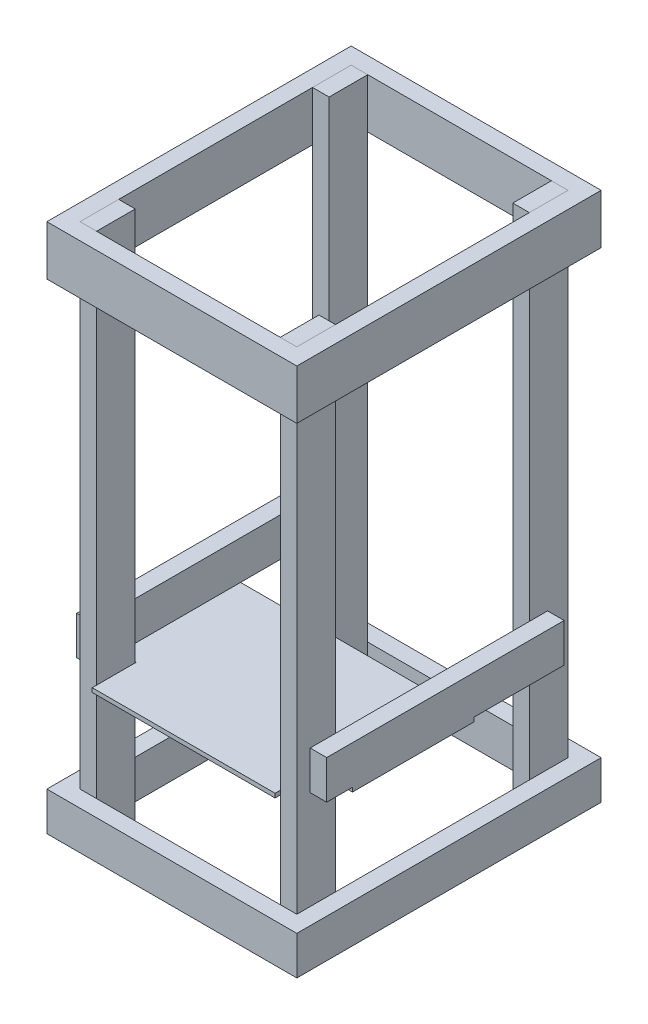
SolidWorks part; units mm, degrees
ref_plane "Front Plane" through (0, 0, 0) normal (0, 0, 1) x (1, 0, 0)
ref_plane "Top Plane" through (0, 0, 0) normal (0, 1, 0) x (1, 0, 0)
ref_plane "Right Plane" through (0, 0, 0) normal (1, 0, 0) x (0, 0, -1)
sketch "Sketch1" plane through (0, 0, 0) normal (0, 1, 0) x (1, 0, 0)
  line L0 (-130.4222, 311.9) -> (-130.4222, 350) construction
  line L1 (-287.5, 350) -> (287.5, 350)
  line L2 (-287.5, 350) -> (-287.5, -350)
  line L3 (-287.5, -350) -> (287.5, -350)
  line L4 (287.5, 350) -> (287.5, -350)
  line L5 (-287.5, 350) -> (287.5, -350) construction
  line L6 (-287.5, -350) -> (287.5, 350) construction
  line L7 (-249.4, 311.9) -> (249.4, 311.9)
  line L8 (-249.4, 311.9) -> (-249.4, -311.9)
  line L9 (-249.4, -311.9) -> (249.4, -311.9)
  line L10 (249.4, 311.9) -> (249.4, -311.9)
  line L11 (-249.4, 311.9) -> (249.4, -311.9) construction
  line L12 (-249.4, -311.9) -> (249.4, 311.9) construction
  line L14 (-249.4, 37.6035) -> (-287.5, 37.6035) construction
  line L16 (-62.8311, -311.9) -> (-62.8311, -350) construction
  line L18 (249.4, -90.9147) -> (287.5, -90.9147) construction
  point P0 (0, 0)
  point P6 (0, 0)
  dimension "D1" = 575
  dimension "D2" = 700
  dimension "D3" = 38.1
extrude "Boss-Extrude1" add sketch "Sketch1" along normal blind 114.3
sketch "Sketch2" plane through (0, 114.3, 0) normal (0, -1, 0) x (1, 0, 0)
  line L1 (-249.4, 311.9) -> (-211.3, 311.9)
  line L2 (-249.4, 311.9) -> (-249.4, 223)
  line L3 (-249.4, 223) -> (-211.3, 223)
  line L4 (-211.3, 311.9) -> (-211.3, 223)
  line L5 (-249.4, -311.9) -> (-211.3, -311.9)
  line L6 (-249.4, -311.9) -> (-249.4, -223)
  line L7 (-249.4, -223) -> (-211.3, -223)
  line L8 (-211.3, -311.9) -> (-211.3, -223)
  line L9 (249.4, 311.9) -> (211.3, 311.9)
  line L10 (249.4, 311.9) -> (249.4, 223)
  line L11 (249.4, 223) -> (211.3, 223)
  line L12 (211.3, 311.9) -> (211.3, 223)
  line L19 (249.4, -311.9) -> (211.3, -311.9)
  line L20 (249.4, -311.9) -> (249.4, -223)
  line L21 (249.4, -223) -> (211.3, -223)
  line L22 (211.3, -311.9) -> (211.3, -223)
  dimension "D1" = 38.1
  dimension "D2" = 88.9
extrude "Boss-Extrude2" add sketch "Sketch2" along normal blind 1219.2 separate body
sketch "Sketch3" plane through (0, -1104.9, 0) normal (0, -1, 0) x (1, 0, 0)
  line L0 (249.4, -311.9) -> (-249.4, -311.9) construction
  line L1 (249.4, 311.9) -> (249.4, -311.9) construction
  line L2 (-249.4, 311.9) -> (249.4, 311.9) construction
  line L3 (-249.4, -311.9) -> (-249.4, 311.9) construction
  line L4 (287.5, -350) -> (287.5, 350)
  line L5 (287.5, 350) -> (-287.5, 350)
  line L6 (-287.5, 350) -> (-287.5, -350)
  line L7 (-287.5, -350) -> (287.5, -350)
  line L8 (287.5, -350) -> (287.5, 350)
  line L9 (287.5, 350) -> (-287.5, 350)
  line L10 (-287.5, 350) -> (-287.5, -350)
  line L11 (-287.5, -350) -> (287.5, -350)
  line L12 (249.4, -311.9) -> (-249.4, -311.9)
  line L13 (249.4, 311.9) -> (249.4, -311.9)
  line L14 (-249.4, 311.9) -> (249.4, 311.9)
  line L15 (-249.4, -311.9) -> (-249.4, 311.9)
  dimension "D1" = 0
extrude "Boss-Extrude3" add sketch "Sketch3" against normal blind 88.9
ref_plane "Plane1" through (0, -788.9875, 0) normal (0, 1, 0) x (1, 0, 0)
sketch "Sketch7" plane through (0, -788.9875, 0) normal (0, 1, 0) x (1, 0, 0)
  line L0 (-249.4, 264.9186) -> (-287.5, 264.9186)
  line L1 (-249.4, 311.9) -> (-249.4, -311.9) construction
  line L2 (-287.5, 350) -> (-287.5, -350) construction
  line L3 (-287.5, 264.9186) -> (-287.5, -281.3159)
  line L4 (-287.5, -281.3159) -> (-249.4, -281.3159)
  line L5 (-249.4, 311.9) -> (-249.4, -311.9) construction
  line L6 (-249.4, -281.3159) -> (-249.4, 264.9186)
  line L7 (249.4, 264.9186) -> (287.5, 264.9186)
  line L8 (249.4, -311.9) -> (249.4, 311.9) construction
  line L9 (287.5, -350) -> (287.5, 350) construction
  line L10 (287.5, 264.9186) -> (287.5, -281.3159)
  line L11 (287.5, -281.3159) -> (249.4, -281.3159)
  line L12 (249.4, -281.3159) -> (249.4, 264.9186)
extrude "Boss-Extrude4" add sketch "Sketch7" along normal blind 88.9
sketch "Sketch8" plane through (0, -788.9875, 0) normal (0, -1, 0) x (1, 0, 0)
  line L1 (287.5, -350) -> (287.5, 350) construction
  line L7 (-287.5, 350) -> (-287.5, -350) construction
  line L8 (-287.5, 222) -> (-287.5, -57.4)
  line L9 (-287.5, -57.4) -> (287.5, -57.4)
  line L10 (287.5, -57.4) -> (287.5, 222)
  line L16 (287.5, 281.3159) -> (287.5, -264.9186) construction
  line L17 (-287.5, -264.9186) -> (-287.5, 281.3159) construction
  line L18 (-287.5, 222) -> (-210.3, 222)
  line L19 (-210.3, 222) -> (-210.3, 322.8564)
  line L20 (-210.3, 322.8564) -> (210.3, 322.8564)
  line L21 (210.3, 322.8564) -> (210.3, 222)
  line L22 (210.3, 222) -> (287.5, 222)
  line L23 (211.3, 223) -> (249.4, 223) construction
  line L24 (211.3, 311.9) -> (211.3, 223) construction
  line L25 (-211.3, 223) -> (-211.3, 311.9) construction
  line L26 (-249.4, 223) -> (-211.3, 223) construction
  dimension "D1" = 279.4
  dimension "D2" = 1
  dimension "D3" = 1
  dimension "D4" = 1
extrude "Boss-Extrude8" add sketch "Sketch8" along normal blind 9.525
